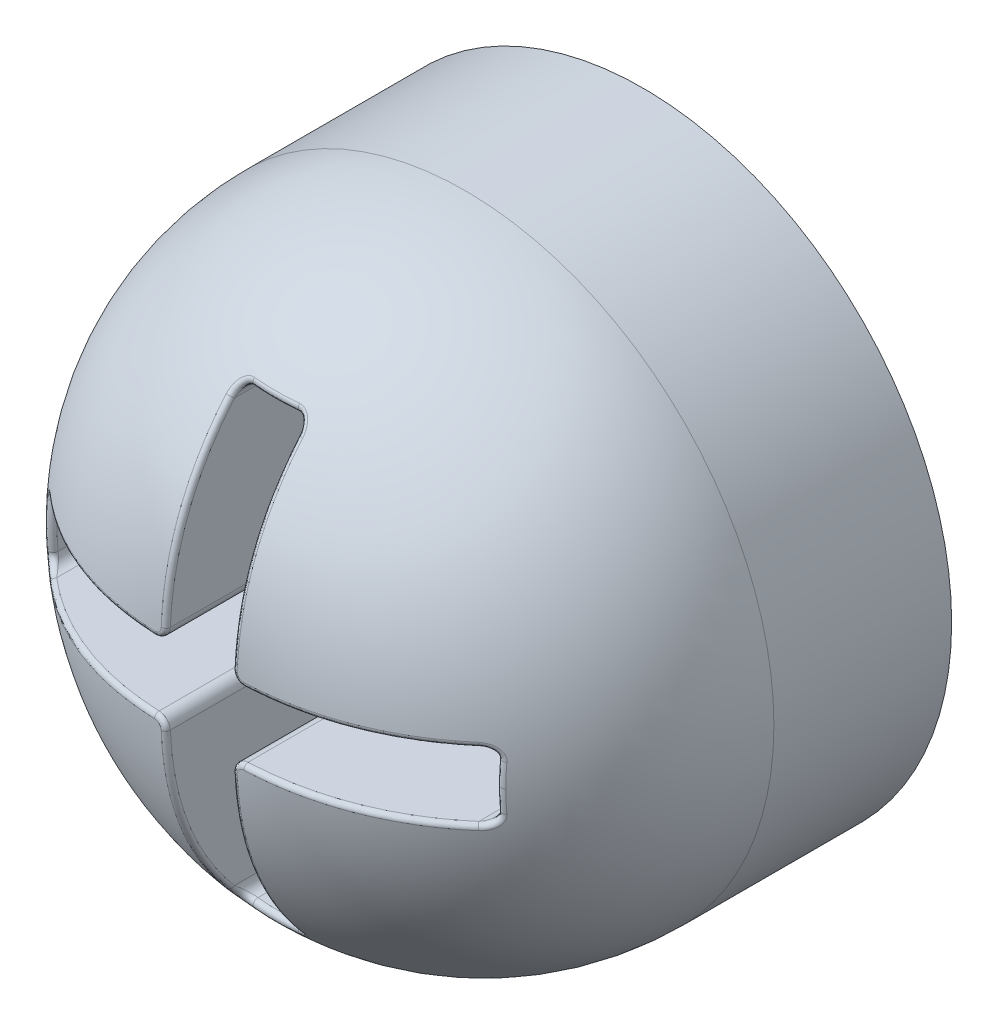
SolidWorks part; units mm, degrees
material "moto_black"
ref_plane "Front Plane" through (0, 0, 0) normal (0, 0, 1) x (1, 0, 0)
ref_plane "Top Plane" through (0, 0, 0) normal (0, 1, 0) x (1, 0, 0)
ref_plane "Right Plane" through (0, 0, 0) normal (1, 0, 0) x (0, 0, -1)
sketch "Sketch1" plane through (0, 0, 0) normal (0, 0, 1) x (1, 0, 0)
  circle A0 centre (0, 0) radius 13.89
  dimension "D1" = 27.78
extrude "Boss-Extrude1" add sketch "Sketch1" along normal blind 20
sketch "Sketch2" plane through (0, 0, 20) normal (0, 0, 1) x (1, 0, 0)
  line L1 (-1.5, -10) -> (1.5, -10)
  line L2 (-1.5, -10) -> (-1.5, 10)
  line L3 (-1.5, 10) -> (1.5, 10)
  line L4 (1.5, -10) -> (1.5, 10)
  line L5 (-1.5, -10) -> (1.5, 10) construction
  line L6 (-1.5, 10) -> (1.5, -10) construction
  line L7 (-10, -1.5) -> (10, -1.5)
  line L8 (-10, -1.5) -> (-10, 1.5)
  line L9 (-10, 1.5) -> (10, 1.5)
  line L10 (10, -1.5) -> (10, 1.5)
  line L11 (-10, -1.5) -> (10, 1.5) construction
  line L12 (-10, 1.5) -> (10, -1.5) construction
  point P0 (0, 0)
  point P6 (0, 0)
  dimension "D1" = 3
  dimension "D2" = 3
  dimension "D3" = 20
  dimension "D4" = 20
extrude "Cut-Extrude1" cut sketch "Sketch2" against normal blind 7 contours L2 L9 L4 L3 | L7 L10 L9 L4 | L9 L2 L7 L4 | L9 L8 L7 L2 | L7 L2 L1 L4 region at (0, -5.75, 20) region at (-5.75, 0, 20) region at (0, 0, 20) region at (5.75, 0, 20) region at (0, 5.75, 20)
fillet "Fillet1" radius 12 1 edges at (13.89, 0, 20)
fillet "Fillet2" radius 0.5 4 edges at (1.5, -1.5, 16.4989) (-1.5, -1.5, 16.4989) (-1.5, 1.5, 16.4989) (1.5, 1.5, 16.4989)
fillet "Fillet3" radius 0.5 8 edges at (-1.5, 10, 14.8704) (1.5, 10, 14.8704) (10, 1.5, 14.8704) (10, -1.5, 14.8704) (1.5, -10, 14.8704) (-1.5, -10, 14.8704) (-10, -1.5, 14.8704) (-10, 1.5, 14.8704)
fillet "Fillet4" radius 0.2 25 edges at (9.933, -1.25, 16.8342) (9.8419, 1.3648, 16.9028) (6.6336, 1.5, 18.949) (1.6093, 1.6879, 19.9919) (1.5, 3.6194, 19.8274) (1.25, 9.933, 16.8342) (-1.3648, 9.8419, 16.9028) (-1.5, 6.6336, 18.949) (-1.6879, 1.6093, 19.9919) (-3.6194, 1.5, 19.8274) (-9.933, 1.25, 16.8342) (-9.8419, -1.3648, 16.9028) (-6.6336, -1.5, 18.949) (-1.6093, -1.6879, 19.9919) (-1.5, -3.6194, 19.8274) (-1.25, -9.933, 16.8342) (1.3648, -9.8419, 16.9028) (1.5, -6.6336, 18.949) (1.6879, -1.6093, 19.9919) (3.6194, -1.5, 19.8274)
fillet "Fillet5" radius 0.2 24 edges at (1.6464, 1.6464, 13) (1.5, 5.75, 13) (1.3536, 9.8536, 13) (0, 10, 13) (-1.3536, 9.8536, 13) (-1.5, 5.75, 13) (-1.6464, 1.6464, 13) (-5.75, 1.5, 13) (-9.8536, 1.3536, 13) (-10, 0, 13) (-9.8536, -1.3536, 13) (-5.75, -1.5, 13) (-1.6464, -1.6464, 13) (-1.5, -5.75, 13) (-1.3536, -9.8536, 13) (0, -10, 13) (1.3536, -9.8536, 13) (1.5, -5.75, 13) (1.6464, -1.6464, 13) (5.75, -1.5, 13) (9.8536, -1.3536, 13) (10, 0, 13) (9.8536, 1.3536, 13) (5.75, 1.5, 13)
